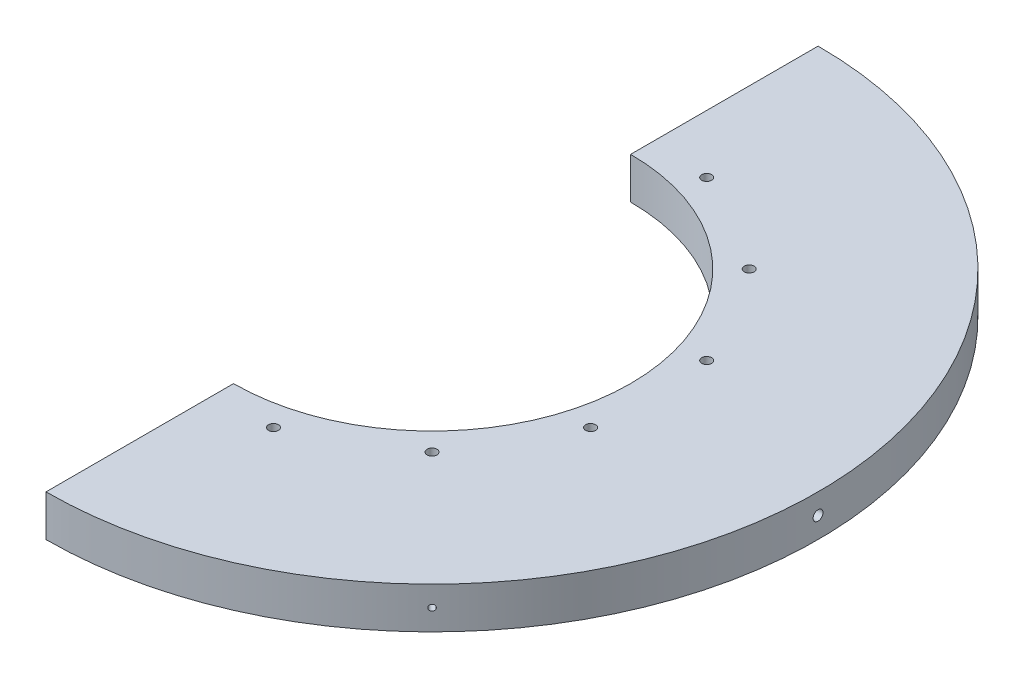
SolidWorks part; units mm, degrees
material "6061-T6 (SS)"
ref_plane "Front Plane" through (0, 0, 0) normal (0, 0, 1) x (1, 0, 0)
ref_plane "Top Plane" through (0, 0, 0) normal (0, 1, 0) x (1, 0, 0)
ref_plane "Right Plane" through (0, 0, 0) normal (1, 0, 0) x (0, 0, -1)
sketch "Sketch1" plane through (0, 0, 0) normal (0, 1, 0) x (1, 0, 0)
  circle A0 centre (0, 0) radius 88.9
  dimension "D1" = 177.8
extrude "Boss-Extrude1" add sketch "Sketch1" along normal blind 9.525
sketch "Sketch2" plane through (0, 9.525, 0) normal (0, 1, 0) x (1, 0, 0)
  circle A0 centre (0, 0) radius 45.72
extrude "Cut-Extrude1" cut sketch "Sketch2" against normal blind 12.7
sketch "Sketch3" plane through (0, 9.525, 0) normal (0, 1, 0) x (1, 0, 0)
  line L0 (0, 0) -> (0, 131.3286) construction
  line L1 (0, 0) -> (35.2548, 131.5728) construction
  circle A1 centre (13.3649, 49.8787) radius 1.143
  point P3 (0, 0)
  dimension "D2" = 51.6382
  dimension "D1" = 2.286
  dimension "D3" = 15
extrude "Cut-Extrude2" cut sketch "Sketch3" against normal blind 12.7
sketch "Sketch5" plane through (0, 9.525, 0) normal (0, 1, 0) x (1, 0, 0)
  line L0 (0, 139.1256) -> (0, -130.5388)
  line L1 (0, -130.5388) -> (-200.055, 4.2934)
  line L2 (-200.055, 4.2934) -> (0, 139.1256)
extrude "Cut-Extrude3" cut sketch "Sketch5" against normal through all both and the other way through all
pattern_circular "CirPattern1" count 12 over 360 about axis through (0, 9.525, 0) along (0, 1, 0) of "Cut-Extrude2"
ref_plane "Plane1" through (88.9, 0, 0) normal (1, 0, 0) x (0, 0, -1)
sketch "Sketch6" plane through (88.9, 0, 0) normal (1, 0, 0) x (0, 0, -1)
  line L0 (0, 0) -> (0, 9.652) construction
  circle A0 centre (0, 4.826) radius 1.143
  dimension "D2" = 2.286
  dimension "D1" = 9.652
extrude "Cut-Extrude4" cut sketch "Sketch6" against normal blind 25.4
ref_plane "Plane2" through (62.8618, 0, 62.8618) normal (0.7071, 0, 0.7071) x (0, -1, 0)
sketch "Sketch7" plane through (62.8618, 0, 62.8618) normal (0.7071, 0, 0.7071) x (0, -1, 0)
  line L0 (0, 0) -> (-9.652, 0) construction
  circle A0 centre (-4.826, 0) radius 0.6985
  dimension "D2" = 1.397
  dimension "D1" = 9.652
extrude "Cut-Extrude5" cut sketch "Sketch7" against normal blind 3.175
pattern_circular "CirPattern2" count 4 over 360 about axis through (0, 9.525, 0) along (0, 1, 0) of "Cut-Extrude5"
